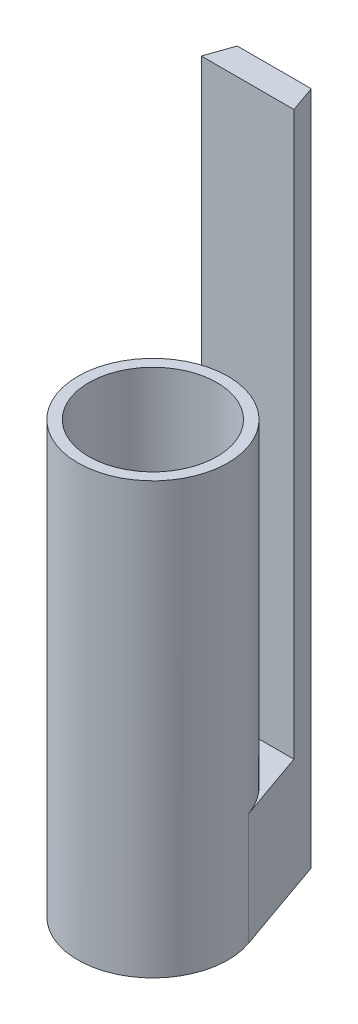
SolidWorks part; units mm, degrees
material "PP Film"
ref_plane "Front Plane" through (0, 0, 0) normal (0, 0, 1) x (1, 0, 0)
ref_plane "Top Plane" through (0, 0, 0) normal (0, 1, 0) x (1, 0, 0)
ref_plane "Right Plane" through (0, 0, 0) normal (1, 0, 0) x (0, 0, -1)
sketch "Sketch3" plane through (0, 0, 0) normal (0, 1, 0) x (1, 0, 0)
  line L0 (0, -5.35) -> (0, 8.65) construction
  line L1 (-2.635, 8.65) -> (2.635, 8.65)
  line L2 (-2.635, 8.65) -> (-5.0483, 1.7711)
  line L3 (2.635, 8.65) -> (5.0483, 1.7711)
  circle A0 centre (0, 0) radius 5.35
  circle A1 centre (0, 0) radius 4.57
  point P8 (0, 8.65)
  dimension "D1" = 10.7
  dimension "D4" = 9.14
  dimension "D2" = 14
  dimension "D3" = 5.27
extrude "Boss-Extrude1" add sketch "Sketch3" along normal blind 30.69 contours A0 L0 A1 | L0 A0 A1 region at (-4.2669, 0, 3.0249) region at (0.1196, 0, 4.96)
extrude "Boss-Extrude2" add sketch "Sketch3<5>" along normal blind 8 contours L0 A0 L3 L1 | A0 L0 L1 L2 region at (-1.9484, 0, -6.4393) region at (1.9484, 0, -6.4393)
sketch "Sketch3<5>" plane through (0, 0, 0) normal (0, 1, 0) x (1, 0, 0) same geometry as "Sketch3"
sketch "Sketch5" plane through (0, 8, 0) normal (0, 1, 0) x (1, 0, 0)
  line L0 (-3.3016, 6.75) -> (3.3016, 6.75)
  line L1 (-2.635, 8.65) -> (-5.0483, 1.7711) construction
  line L2 (2.635, 8.65) -> (5.0483, 1.7711) construction
  line L3 (-2.635, 8.65) -> (2.635, 8.65) construction
  line L4 (-3.3016, 6.75) -> (-2.635, 8.65)
  line L5 (-2.635, 8.65) -> (2.635, 8.65)
  line L6 (2.635, 8.65) -> (3.3016, 6.75)
  dimension "D1" = 1.9
extrude "Boss-Extrude3" add sketch "Sketch5" along normal blind 40.11
extrude "Boss-Extrude4" add sketch "Sketch3<6>" along normal blind 3.48 contours A1 L0 | L0 A1 region at (-1.9396, 0, 0) region at (1.9396, 0, 0)
sketch "Sketch3<6>" plane through (0, 0, 0) normal (0, 1, 0) x (1, 0, 0) same geometry as "Sketch3"
